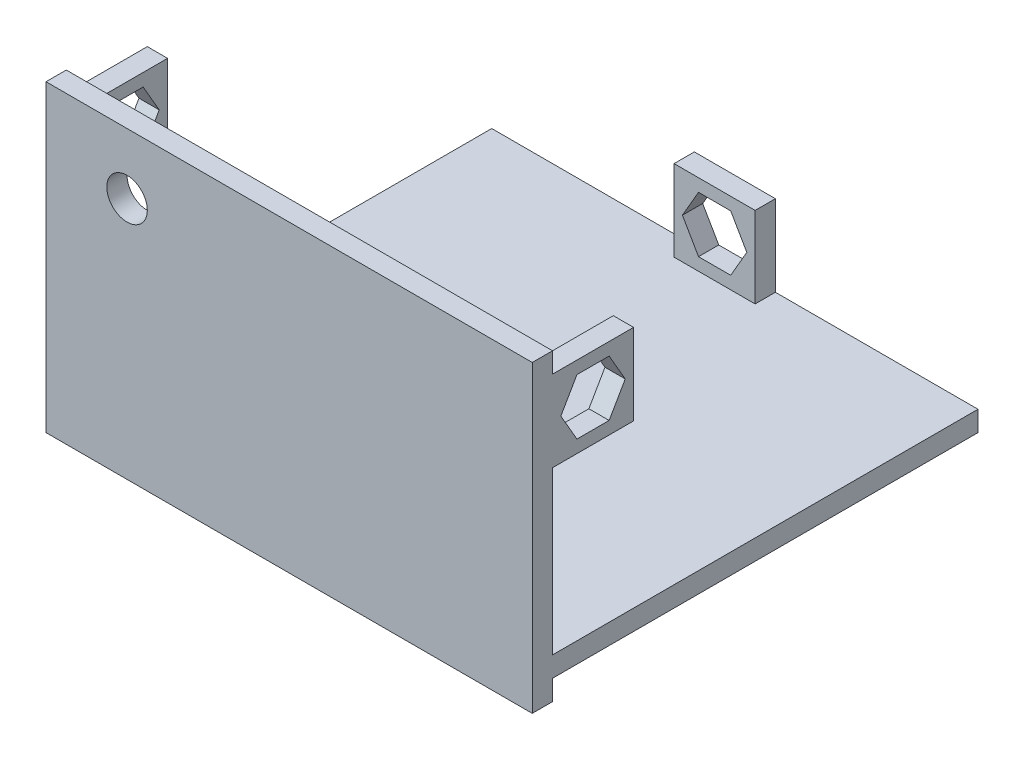
SolidWorks part; units mm, degrees
ref_plane "Front Plane" through (0, 0, 0) normal (0, 0, 1) x (1, 0, 0)
ref_plane "Top Plane" through (0, 0, 0) normal (0, 1, 0) x (1, 0, 0)
ref_plane "Right Plane" through (0, 0, 0) normal (1, 0, 0) x (0, 0, -1)
sketch "Sketch1" plane through (0, 0, 0) normal (0, 0, 1) x (1, 0, 0)
  line L1 (-38.1, -23.8125) -> (38.1, -23.8125)
  line L2 (-38.1, -23.8125) -> (-38.1, 23.8125)
  line L3 (-38.1, 23.8125) -> (38.1, 23.8125)
  line L4 (38.1, -23.8125) -> (38.1, 23.8125)
  line L5 (-38.1, -23.8125) -> (38.1, 23.8125) construction
  line L6 (-38.1, 23.8125) -> (38.1, -23.8125) construction
  point P0 (0, 0)
  dimension "D1" = 76.2
  dimension "D2" = 47.625
extrude "Boss-Extrude1" add sketch "Sketch1" along normal blind 3.175
sketch "Sketch2" plane through (0, 0, 0) normal (0, 0, -1) x (-1, 0, 0)
  line L0 (-38.1, -23.8125) -> (-38.1, 23.8125) construction
  line L1 (-38.1, -20.6375) -> (38.1, -20.6375)
  line L2 (-38.1, -20.6375) -> (-38.1, -17.4625)
  line L3 (-38.1, -17.4625) -> (38.1, -17.4625)
  line L4 (38.1, -20.6375) -> (38.1, -17.4625)
  line L5 (38.1, 23.8125) -> (38.1, -23.8125) construction
  line L6 (38.1, -23.8125) -> (-38.1, -23.8125) construction
  dimension "D1" = 3.175
  dimension "D2" = 3.175
extrude "Boss-Extrude2" add sketch "Sketch2" along normal blind 66.675
sketch "Sketch6" plane through (38.1, 0, 0) normal (1, 0, 0) x (0, 0, -1)
  line L0 (0, -17.4625) -> (0, 23.8125) construction
  line L1 (0, 20.6375) -> (12.7, 20.6375)
  line L2 (0, 20.6375) -> (0, 7.9375)
  line L3 (0, 7.9375) -> (12.7, 7.9375)
  line L4 (12.7, 20.6375) -> (12.7, 7.9375)
  line L5 (-3.175, 23.8125) -> (0, 23.8125) construction
  dimension "D1" = 12.7
  dimension "D2" = 12.7
  dimension "D3" = 3.175
extrude "Boss-Extrude4" add sketch "Sketch6" against normal blind 3.175
sketch "Sketch7" plane through (-38.1, 0, 0) normal (-1, 0, 0) x (0, 0, 1)
  line L0 (0, 23.8125) -> (0, -17.4625) construction
  line L1 (0, 7.9375) -> (-12.7, 7.9375)
  line L2 (0, 7.9375) -> (0, 20.6375)
  line L3 (0, 20.6375) -> (-12.7, 20.6375)
  line L4 (-12.7, 7.9375) -> (-12.7, 20.6375)
  dimension "D1" = 12.7
  dimension "D2" = 12.7
  dimension "D3" = 3.175
extrude "Boss-Extrude5" add sketch "Sketch7" against normal blind 3.175
sketch "Sketch8" plane through (0, 0, -66.675) normal (0, 0, -1) x (-1, 0, 0)
  line L0 (38.1, -17.4625) -> (-38.1, -17.4625) construction
  line L1 (-6.35, -17.4625) -> (6.35, -17.4625)
  line L2 (-6.35, -17.4625) -> (-6.35, -4.7625)
  line L3 (-6.35, -4.7625) -> (6.35, -4.7625)
  line L4 (6.35, -17.4625) -> (6.35, -4.7625)
  point P6 (0, -17.4625)
  dimension "D1" = 12.7
  dimension "D2" = 12.7
extrude "Boss-Extrude6" add sketch "Sketch8" against normal blind 3.175
sketch "Sketch9" plane through (0, 0, -66.675) normal (0, 0, -1) x (-1, 0, 0)
  line L1 (2.5223, -6.7437) -> (-2.5223, -6.7437)
  line L2 (-2.5223, -6.7437) -> (-5.0447, -11.1125)
  line L3 (-5.0447, -11.1125) -> (-2.5223, -15.4813)
  line L4 (-2.5223, -15.4813) -> (2.5223, -15.4813)
  line L5 (2.5223, -15.4813) -> (5.0447, -11.1125)
  line L6 (5.0447, -11.1125) -> (2.5223, -6.7437)
  line L8 (6.35, -4.7625) -> (-6.35, -4.7625) construction
  line L9 (-6.35, -4.7625) -> (-6.35, -17.4625) construction
  circle A0 centre (0, -11.1125) radius 4.3688 construction
  dimension "D1" = 8.7376
  dimension "D2" = 6.35
  dimension "D3" = 6.35
extrude "Cut-Extrude4" cut sketch "Sketch9" against normal blind 3.175 contours L1 L2 L3 L4 L5 L6
sketch "Sketch10" plane through (38.1, 0, 0) normal (1, 0, 0) x (0, 0, -1)
  line L0 (12.7, 20.6375) -> (0, 20.6375) construction
  line L1 (11.3947, 14.2875) -> (8.8723, 18.6563)
  line L2 (8.8723, 18.6563) -> (3.8277, 18.6563)
  line L3 (3.8277, 18.6563) -> (1.3053, 14.2875)
  line L4 (1.3053, 14.2875) -> (3.8277, 9.9187)
  line L5 (3.8277, 9.9187) -> (8.8723, 9.9187)
  line L6 (8.8723, 9.9187) -> (11.3947, 14.2875)
  line L7 (12.7, 7.9375) -> (12.7, 20.6375) construction
  circle A0 centre (6.35, 14.2875) radius 4.3688 construction
  dimension "D1" = 8.7376
  dimension "D2" = 6.35
  dimension "D3" = 6.35
extrude "Cut-Extrude5" cut sketch "Sketch10" against normal through all both and the other way through all
sketch "Sketch11" plane through (0, 0, 3.175) normal (0, 0, 1) x (1, 0, 0)
  line L0 (-38.1, 23.8125) -> (-38.1, 20.6375) construction
  line L1 (38.1, 23.8125) -> (-38.1, 23.8125) construction
  circle A0 centre (-25.4, 14.2875) radius 3.175
  dimension "D1" = 6.35
  dimension "D2" = 12.7
  dimension "D3" = 9.525
extrude "Cut-Extrude6" cut sketch "Sketch11" against normal blind 3.175
